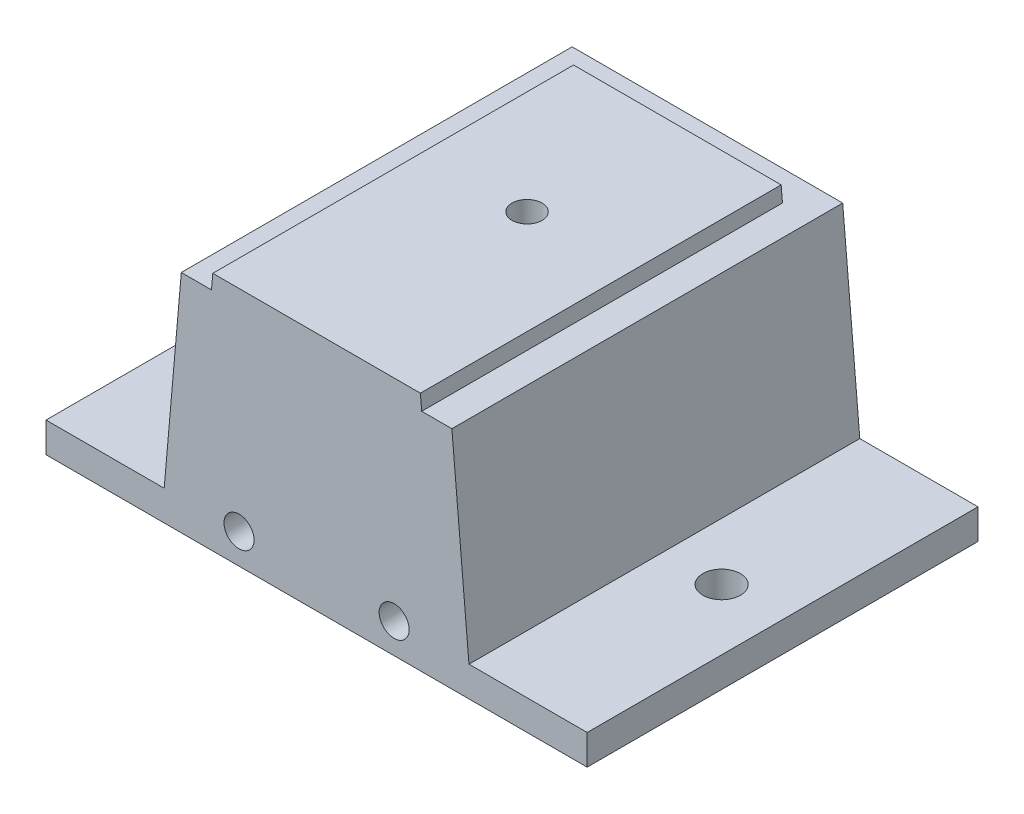
SolidWorks part; units mm, degrees
material "6061 Alloy"
ref_plane "Front Plane" through (0, 0, 0) normal (0, 0, 1) x (1, 0, 0)
ref_plane "Top Plane" through (0, 0, 0) normal (0, 1, 0) x (1, 0, 0)
ref_plane "Right Plane" through (0, 0, 0) normal (1, 0, 0) x (0, 0, -1)
sketch "Sketch1" plane through (0, 0, 0) normal (0, 0, 1) x (1, 0, 0)
  line L0 (0, 0) -> (0, 65.9076) construction
  line L1 (57.15, 0) -> (-57.15, 0)
  line L2 (-57.15, 0) -> (-57.15, 6.35)
  line L3 (-57.15, 6.35) -> (-32.1861, 6.35)
  line L4 (-32.1861, 6.35) -> (-28.575, 47.625)
  line L5 (-21.923, 50.8) -> (21.923, 50.8)
  line L6 (57.15, 0) -> (57.15, 6.35)
  line L7 (57.15, 6.35) -> (32.1861, 6.35)
  line L8 (32.1861, 6.35) -> (28.575, 47.625)
  line L9 (-28.575, 47.625) -> (-22.2007, 47.625)
  line L10 (-22.2007, 47.625) -> (-21.923, 50.8)
  line L11 (21.923, 50.8) -> (22.2007, 47.625)
  line L12 (22.2007, 47.625) -> (28.575, 47.625)
  point P12 (0, 50.8)
  point P15 (-22.0619, 49.2125)
  dimension "D3" = 50.8
  dimension "D4" = 95
  dimension "D6" = 3.175
extrude "Boss-Extrude1" add sketch "Sketch1" along normal mid plane 82.55
shell "Shell1" thickness 6.35 removed face at (0, 0, 0)
sketch "Sketch7" plane through (0, 0, 0) normal (1, 0, 0) x (0, 0, -1)
  line L0 (41.275, 47.625) -> (34.925, 47.625)
  line L2 (-41.275, 47.625) -> (41.275, 47.625) construction
  line L3 (34.925, 47.625) -> (34.925, 50.8)
  line L4 (-41.275, 50.8) -> (41.275, 50.8) construction
  line L5 (34.925, 50.8) -> (41.275, 50.8)
  line L6 (41.275, 50.8) -> (41.275, 47.625)
  dimension "D1" = 6.35
extrude "Cut-Extrude2" cut sketch "Sketch7" against normal through all both and the other way through all
sketch "Sketch8" plane through (0, 0, -50.8) normal (0, 1, 0) x (1, 0, 0)
  line L4 (0, -78.74) -> (0, -22.86) construction
  circle A1 centre (44.2781, -50.8) radius 3.9687
  circle A2 centre (-44.2781, -50.8) radius 3.9687
  point P2 (0, -69.2468)
  point P3 (0, 0)
  point P8 (44.2781, -50.8)
  point P16 (0, -93.98)
  point P17 (0, -93.98)
  point P19 (44.45, -10.795)
  dimension "D5" = 7.9375
extrude "Cut-Extrude3" cut sketch "Sketch8" along normal through all
hole_wizard "1/4 (0.25) Diameter Hole1" positions "Sketch9" profile "Sketch10" hole size "1/4" standard "ANSI Inch" end condition up to next
sketch "Sketch9" plane through (0, 50.8, 0) normal (0, 1, 0) x (1, 0, 0)
  line L0 (0, 0) -> (0, 25.0279) construction
  point P0 (0, 3.175)
  point P10 (-7.6794, 3.175)
  point P11 (0, 3.1482)
  point P12 (8.4035, 5.4229)
  point P14 (-0.0419, 3.175)
sketch "Sketch10" plane through (0, 50.8, -3.175) normal (1, 0, 0) x (0, 0, 1)
  line L0 (0, 0) -> (0, 6.35)
  line L1 (0, 6.35) -> (3.175, 6.35)
  line L2 (3.175, 6.35) -> (3.175, 0)
  line L5 (3.175, 0) -> (0, 0)
  line L11 (0, -6.35) -> (0, 107.95) construction
  dimension "Thru Hole Dia." = 6.35
  dimension "Thru Hole Depth" = 6.35
hole_wizard "1/4 (0.25) Diameter Hole2" positions "Sketch11" profile "Sketch12" hole size "1/4" standard "ANSI Inch" end condition through all
sketch "Sketch11" plane through (0, 0, -41.275) normal (0, 0, -1) x (-1, 0, 0)
  point P0 (-16.382, 6.35)
  point P3 (16.382, 6.35)
sketch "Sketch12" plane through (16.382, 6.35, -41.275) normal (1, 0, 0) x (0, 1, 0)
  line L0 (0, 0) -> (0, 82.55)
  line L1 (0, 82.55) -> (3.175, 82.55)
  line L2 (3.175, 82.55) -> (3.175, 0)
  line L5 (3.175, 0) -> (0, 0)
  line L11 (0, -6.35) -> (0, 107.95) construction
  dimension "Thru Hole Dia." = 6.35
  dimension "Thru Hole Depth" = 82.55
equation "\"BedBaseDraftAngle\"=95"
equation "\"D4@Sketch1\"=\"BedBaseDraftAngle\""
